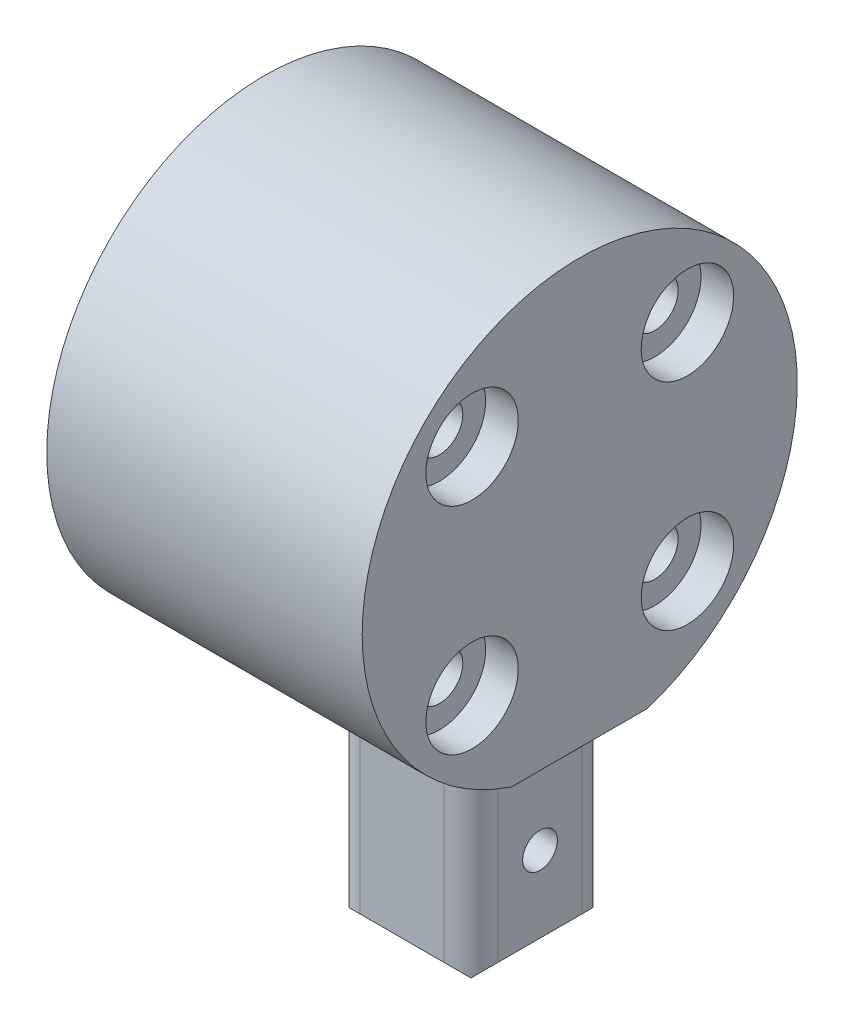
SolidWorks part; units mm, degrees
ref_plane "前视基准面" through (0, 0, 0) normal (0, 0, 1) x (1, 0, 0)
ref_plane "上视基准面" through (0, 0, 0) normal (0, 1, 0) x (1, 0, 0)
ref_plane "右视基准面" through (0, 0, 0) normal (1, 0, 0) x (0, 0, -1)
sketch "草图1" plane through (0, 0, 0) normal (1, 0, 0) x (0, 0, -1)
  circle A0 centre (0, 0) radius 20
  dimension "D1" = 40
extrude "凸台-拉伸1" add sketch "草图1" along normal blind 10
sketch "草图2" plane through (0, 0, 0) normal (-1, 0, 0) x (0, 0, 1)
  line L1 (-7.5, -15.25) -> (7.5, -15.25)
  line L2 (-7.5, -15.25) -> (-7.5, 15.25)
  line L3 (-7.5, 15.25) -> (7.5, 15.25)
  line L4 (7.5, -15.25) -> (7.5, 15.25)
  line L5 (-7.5, -15.25) -> (7.5, 15.25) construction
  line L6 (-7.5, 15.25) -> (7.5, -15.25) construction
  point P0 (0, 0)
  dimension "D1" = 15
  dimension "D2" = 30.5
extrude "切除-拉伸1" cut sketch "草图2" against normal blind 4
sketch "草图3" plane through (4, 0, 0) normal (-1, 0, 0) x (0, 0, 1)
  circle A0 centre (0, 0) radius 8.75
  dimension "D1" = 17.5
extrude "切除-拉伸2" cut sketch "草图3" along normal blind 4
sketch "草图4" plane through (0, 0, 0) normal (-1, 0, 0) x (0, 0, 1)
  line L1 (-9, -16) -> (9, -16)
  line L2 (-9, -16) -> (-9, 16)
  line L3 (-9, 16) -> (9, 16)
  line L4 (9, -16) -> (9, 16)
  line L5 (-9, -16) -> (9, 16) construction
  line L6 (-9, 16) -> (9, -16) construction
  circle A0 centre (0, 0) radius 20
  dimension "D3" = 40
  dimension "D1" = 32
  dimension "D2" = 18
extrude "凸台-拉伸2" add sketch "草图4" along normal blind 19
fillet "圆角1" radius 3 4 edges at (-9.5, -16, -9) (-9.5, -16, 9) (-9.5, 16, -9) (-9.5, 16, 9)
sketch "草图5" plane through (-19, 0, 0) normal (-1, 0, 0) x (0, 0, 1)
  line L0 (-6, -16) -> (6, -16) construction
  line L1 (6, 16) -> (-6, 16) construction
  circle A0 centre (0, -16) radius 2.5
  circle A1 centre (0, 16) radius 2.5
  dimension "D1" = 5
  dimension "D2" = 5
extrude "切除-拉伸3" cut sketch "草图5" against normal blind 20
fillet "圆角2" radius 3 4 edges at (-9.5, -16, -2.5) (-9.5, -16, 2.5) (-9.5, 16, -2.5) (-9.5, 16, 2.5)
sketch "草图6" plane through (10, 0, 0) normal (1, 0, 0) x (0, 0, -1)
  line L0 (0, 0) -> (20, 0) construction
  line L1 (0, 0) -> (18.216, -18.216) construction
  circle A0 centre (0, 0) radius 14 construction
  circle A2 centre (9.8995, -9.8995) radius 2.15
  circle A3 centre (0, 0) radius 14 construction
  circle A4 centre (-9.8995, -9.8995) radius 2.15
  circle A5 centre (0, 0) radius 14 construction
  circle A6 centre (-9.8995, 9.8995) radius 2.15
  circle A7 centre (0, 0) radius 14 construction
  circle A8 centre (9.8995, 9.8995) radius 2.15
  point P21 (0, 0)
  dimension "D1" = 28
  dimension "D3" = 4.3
  dimension "D2" = 45
  dimension "D4" = 4
extrude "切除-拉伸4" cut sketch "草图6" against normal blind 43
fillet "圆角3" radius 1 8 edges at (-9.5, -11.8523, 9) (-9.5, -7.9467, 9) (-9.5, -11.8523, -9) (-9.5, -7.9467, -9) (-9.5, 7.9467, -9) (-9.5, 11.8523, -9) (-9.5, 7.9467, 9) (-9.5, 11.8523, 9)
sketch "草图7" plane through (10, 0, 0) normal (1, 0, 0) x (0, 0, -1)
  circle A0 centre (9.8995, -9.8995) radius 4.25
  dimension "D1" = 8.5
extrude "切除-拉伸5" cut sketch "草图7" against normal blind 3
pattern_circular "阵列(圆周)1" count 4 over 360 about axis through (10, 0, 0) along (1, 0, 0) of "切除-拉伸5"
sketch "草图8" plane through (10, 0, 0) normal (1, 0, 0) x (0, 0, -1)
  line L1 (-11.4701, -19) -> (11.4701, -19)
  line L2 (-11.4701, -19) -> (-11.4701, -28.3124)
  line L3 (-11.4701, -28.3124) -> (11.4701, -28.3124)
  line L4 (11.4701, -19) -> (11.4701, -28.3124)
  line L5 (-11.4701, -19) -> (11.4701, -28.3124) construction
  line L6 (-11.4701, -28.3124) -> (11.4701, -19) construction
  point P0 (0, -23.6562)
  dimension "D1" = 19
extrude "切除-拉伸6" cut sketch "草图8" against normal blind 23
sketch "草图9" plane through (0, -19, 0) normal (0, -1, 0) x (1, 0, 0)
  line L1 (-3, -3) -> (3, -3)
  line L2 (-3, -3) -> (-3, 3)
  line L3 (-3, 3) -> (3, 3)
  line L4 (3, -3) -> (3, 3)
  line L5 (-3, -3) -> (3, 3) construction
  line L6 (-3, 3) -> (3, -3) construction
  point P0 (0, 0)
  dimension "D1" = 6
  dimension "D2" = 6
extrude "切除-拉伸7" cut sketch "草图9" against normal blind 4
sketch "草图10" plane through (0, -19, 0) normal (0, -1, 0) x (1, 0, 0)
  line L0 (10, -6.245) -> (10, 6.245) construction
  line L1 (-6.35, -6.35) -> (6.35, -6.35)
  line L2 (-6.35, -6.35) -> (-6.35, 6.35)
  line L3 (-6.35, 6.35) -> (6.35, 6.35)
  line L4 (6.35, -6.35) -> (6.35, 6.35)
  line L5 (-6.35, -6.35) -> (6.35, 6.35) construction
  line L6 (-6.35, 6.35) -> (6.35, -6.35) construction
  line L7 (-3, -3) -> (3, -3)
  line L8 (-3, -3) -> (-3, 3)
  line L9 (-3, 3) -> (3, 3)
  line L10 (3, -3) -> (3, 3)
  line L11 (-3, -3) -> (3, 3) construction
  line L12 (-3, 3) -> (3, -3) construction
  point P0 (0, 0)
  point P6 (0, 0)
  dimension "D1" = 12.7
  dimension "D2" = 12.7
  dimension "D3" = 10
extrude "凸台-拉伸3" add sketch "草图10" along normal blind 20 and the other way blind 0.5
sketch "草图11" plane through (-6.35, 0, 0) normal (-1, 0, 0) x (0, 0, 1)
  line L0 (-6.245, -19) -> (6.245, -19) construction
  line L1 (6.35, -18.9652) -> (6.35, -39) construction
  line L2 (-6.35, -18.9652) -> (-6.35, -39) construction
  circle A0 centre (0, -29) radius 1.6
  dimension "D1" = 3.2
  dimension "D2" = 10
  dimension "D3" = 6.35
  dimension "D4" = 6.35
extrude "切除-拉伸8" cut sketch "草图11" against normal blind 20
chamfer "倒角1" distance 3 angle 45 2 edges at (-3, -27.7342, -3) (-3, -27.7342, 3)
fillet "圆角4" radius 2 4 edges at (-0.5003, -16.8675, 2.4997) (-0.5003, -16.8675, -2.4997) (-1.8082, -18.1976, 1.1918) (-1.8082, -18.1976, -1.1918)
chamfer "倒角2" distance 3 angle 45 4 edges at (6.35, -39, 0) (0, -39, -6.35) (-6.35, -39, 0) (0, -39, 6.35)
sketch "草图13" plane through (0, -39, 0) normal (0, -1, 0) x (1, 0, 0)
  circle A0 centre (0, 0) radius 3.35
  dimension "D1" = 6.7
fillet "圆角5" radius 2.5 4 edges at (6.35, -27.4826, -6.35) (6.35, -27.4826, 6.35) (-6.35, -27.4826, 6.35) (-6.35, -27.4826, -6.35)
chamfer "倒角3" distance 1 angle 45 1 edges at (-13, -19, 0)
